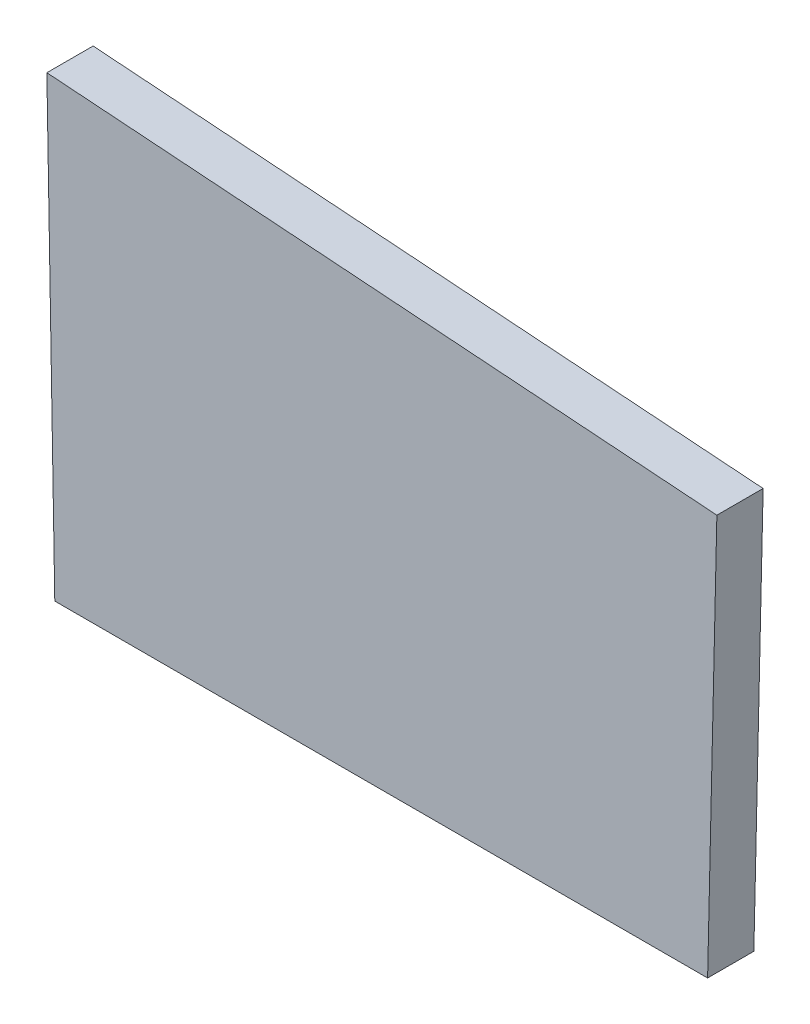
SolidWorks part; units mm, degrees
ref_plane "Ebene vorne" through (0, 0, 0) normal (0, 0, 1) x (1, 0, 0)
ref_plane "Ebene oben" through (0, 0, 0) normal (0, 1, 0) x (1, 0, 0)
ref_plane "Ebene rechts" through (0, 0, 0) normal (1, 0, 0) x (0, 0, -1)
sketch "Skizze1" plane through (0, 0, 0) normal (0, 0, 1) x (1, 0, 0)
  line L0 (0, 0) -> (-0.3424, 19.617)
  line L1 (-0.3424, 19.617) -> (28.631, 17.5334)
  line L2 (28.631, 17.5334) -> (28.23, 0)
  line L3 (28.23, 0) -> (0, 0)
  dimension "D1" = 28.23
  dimension "D2" = 17.538
  dimension "D3" = 19.62
  dimension "D4" = 91
  dimension "D5" = 91.31
extrude "Aufsatz-Linear austragen1" add sketch "Skizze1" along normal blind 2
sketch "Skizze4" plane through (0, 0, 0) normal (0, 0, 1) x (1, 0, 0)
  line L1 (0, 0) -> (30, 0)
  line L2 (0, 0) -> (0, 20)
  line L3 (0, 20) -> (30, 20)
  line L4 (30, 0) -> (30, 20)
  dimension "D1" = 30
  dimension "D2" = 20
sketch "Skizze2" plane through (0, 0, 2) normal (0, 0, 1) x (1, 0, 0)
  circle A0 centre (13.531, 10.0477) radius 16.8536
sketch "Skizze3" plane through (0, 0, 2) normal (0, 0, 1) x (1, 0, 0)
  line L0 (0.1443, -0.2333) -> (28.1443, -0.2333)
  line L1 (0.1443, -0.2333) -> (0.1443, 17.7667)
  line L2 (28.1443, -0.2333) -> (28.1443, 17.7667)
  line L3 (0.1443, 17.7667) -> (28.1443, 17.7667)
  line L4 (0.1443, -0.2333) -> (28.1443, 17.7667) construction
  line L5 (28.1443, -0.2333) -> (0.1443, 17.7667) construction
  line L6 (28.23, 0) -> (28.631, 17.5334) construction
  line L7 (28.631, 17.5334) -> (-0.3424, 19.617) construction
  point P1 (14.1443, 8.7667)
  point P8 (28.4305, 8.7667)
  point P11 (14.1443, 18.5752)
  dimension "D1" = 18
  dimension "D2" = 28
ref_point "SWASI_Vision_Point_1"
ref_point "SWASI_Vision_Point_1_helper"
ref_point "SWASI_Vision_Point_2"
ref_point "SWASI_Vision_Point_2_helper"
ref_point "SWASI_Vision_Point_3"
ref_point "SWASI_Vision_Point_3_helper"
ref_point "SWASI_Vision_Point_4"
ref_plane "SWASI_Alignment_Plane_1" through (0, 0, 0) normal (0, -1, 0) x (-1, 0, 0)
ref_plane "SWASI_Alignment_Plane_2ddasd" through (0, 0, 0) normal (0, 0, 1) x (1, 0, 0)
ref_axis "Achse1" through (28.23, 0, 2) along (-1, 0, 0)
ref_axis "Achse2" through (0, 0, 2) along (0.9975, 0, -0.0707)
ref_axis "Achse3" through (0, 0, 0) along (0.9975, 0, 0.0707)
ref_point "SWASI_Surface_Center_Point"
ref_axis "Achse5" through (0, 0, 2) along (0, 0, -1)
ref_axis "SWASI_Norm_Alignment_Plane_3" through (28.23, 0, 0) along (-1, 0, 0)
ref_plane "SWASI_Alignment_Plane_3" through (14.115, 0, 1) normal (-1, 0, 0) x (0, 0, 1)
ref_point "Punkt1"
ref_point "Punkt2"
